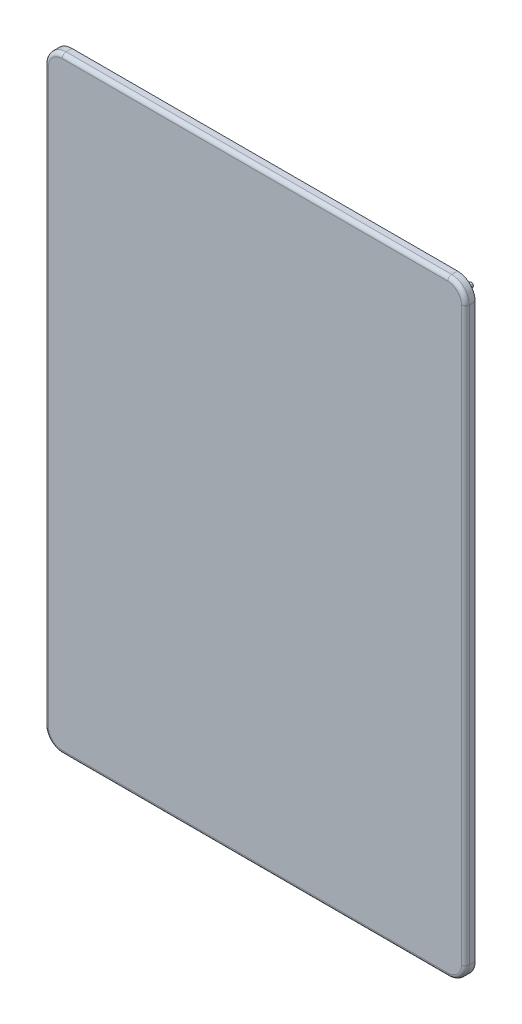
SolidWorks part; units mm, degrees
ref_plane "Front Plane" through (0, 0, 0) normal (0, 0, 1) x (1, 0, 0)
ref_plane "Top Plane" through (0, 0, 0) normal (0, 1, 0) x (1, 0, 0)
ref_plane "Right Plane" through (0, 0, 0) normal (1, 0, 0) x (0, 0, -1)
sketch "Sketch1" plane through (0, 0, 0) normal (0, 0, 1) x (1, 0, 0)
  line L1 (0, 0) -> (273.05, 0)
  line L2 (0, 0) -> (0, 393.7)
  line L3 (0, 393.7) -> (273.05, 393.7)
  line L4 (273.05, 0) -> (273.05, 393.7)
  dimension "D1" = 393.7
  dimension "D2" = 273.05
extrude "Boss-Extrude1" add sketch "Sketch1" along normal blind 6.35
fillet "Fillet2" radius 11.43 4 edges at (0, 0, 3.175) (273.05, 0, 3.175) (0, 393.7, 3.175) (273.05, 393.7, 3.175)
fillet "Fillet1" radius 2.54 8 edges at (136.525, 393.7, 6.35) (273.05, 196.85, 6.35) (136.525, 0, 6.35) (0, 196.85, 6.35) (3.3478, 390.3522, 6.35) (269.7022, 390.3522, 6.35) (269.7022, 3.3478, 6.35) (3.3478, 3.3478, 6.35)
sketch "Sketch2" plane through (0, 0, 0) normal (0, 0, -1) x (-1, 0, 0)
  line L0 (-265.811, 385.826) -> (-7.239, 385.826) construction
  line L1 (-7.239, 385.826) -> (-7.239, 7.874) construction
  line L2 (-7.239, 7.874) -> (-265.811, 7.874) construction
  line L3 (-265.811, 7.874) -> (-265.811, 385.826) construction
  line L4 (-136.525, 393.7) -> (-136.525, 385.826) construction
  line L5 (-261.62, 393.7) -> (-11.43, 393.7) construction
  line L6 (-273.05, 196.85) -> (-265.811, 196.85) construction
  line L7 (-273.05, 11.43) -> (-273.05, 382.27) construction
  circle A0 centre (-265.811, 385.826) radius 1.397
  circle A1 centre (-136.525, 385.826) radius 1.397
  circle A2 centre (-7.239, 385.826) radius 1.397
  circle A3 centre (-136.525, 196.85) radius 1.397 [skipped]
  circle A4 centre (-7.239, 196.85) radius 1.397
  circle A5 centre (-136.525, 7.874) radius 1.397
  circle A6 centre (-7.239, 7.874) radius 1.397
  circle A7 centre (-265.811, 196.85) radius 1.397
  circle A8 centre (-265.811, 7.874) radius 1.397
  dimension "D1" = 2.794
  dimension "D2" = 3
  dimension "D3" = 3
extrude "Boss-Extrude2" add sketch "Sketch2" along normal blind 4.699
ref_plane "Plane1" through (0, 9.779, 0) normal (0, -1, 0) x (-1, 0, 0)
sketch "Sketch3" plane through (0, 9.779, 0) normal (0, -1, 0) x (-1, 0, 0)
  line L0 (-240.03, 0) -> (-240.03, 0.254)
  line L1 (-11.43, 0) -> (-261.62, 0) construction
  line L2 (-240.03, 0.254) -> (-233.7435, 0.254)
  line L3 (-221.869, 0.254) -> (-221.869, 0)
  line L4 (-221.869, 0) -> (-240.03, 0)
  line L5 (-273.05, -3.81) -> (-273.05, 0) construction
  line L6 (-230.9495, 0.254) -> (-230.9495, 1.27) construction
  line L7 (-232.9815, 1.27) -> (-232.9815, 1.016)
  line L8 (-228.9175, 1.27) -> (-228.9175, 1.016)
  line L9 (-228.1555, 0.254) -> (-221.869, 0.254)
  arc A0 (-228.1555, 0.254) -> (-228.9175, 1.016) centre (-228.1555, 1.016) cw
  arc A1 (-228.9175, 1.27) -> (-232.9815, 1.27) centre (-230.9495, 1.27) ccw
  arc A2 (-233.7435, 0.254) -> (-232.9815, 1.016) centre (-233.7435, 1.016) ccw
  point P16 (-228.9175, 0.254)
  dimension "D4" = 0.762
  dimension "D1" = 18.161
  dimension "D2" = 33.02
  dimension "D3" = 0.254
  dimension "D5" = 1.27
extrude "Boss-Extrude3" add sketch "Sketch3" against normal blind 6.35
